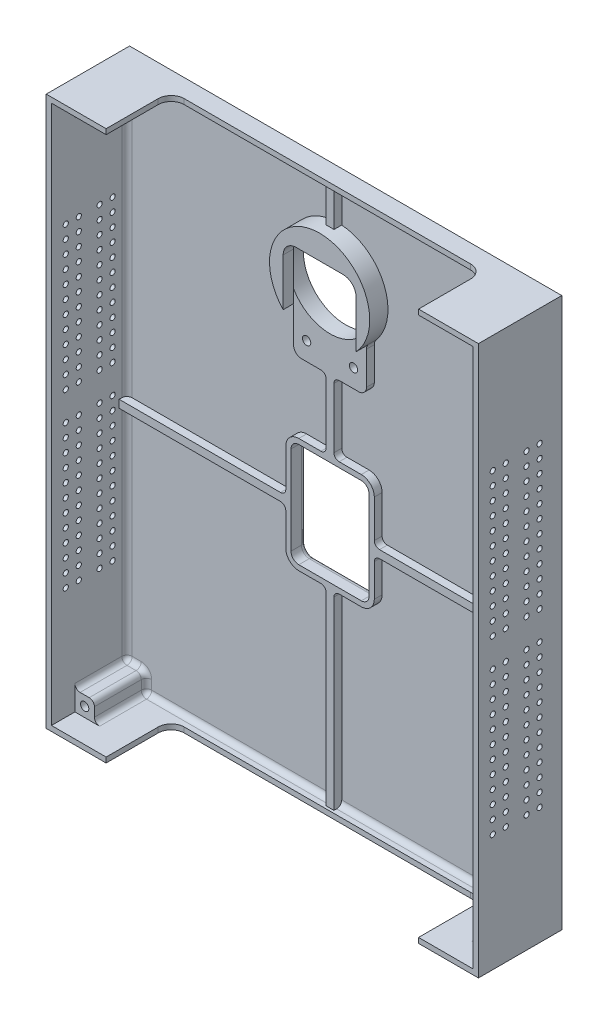
SolidWorks part; units mm, degrees
ref_plane "Front Plane" through (0, 0, 0) normal (0, 0, 1) x (1, 0, 0)
ref_plane "Top Plane" through (0, 0, 0) normal (0, 1, 0) x (1, 0, 0)
ref_plane "Right Plane" through (0, 0, 0) normal (1, 0, 0) x (0, 0, -1)
ref_plane "Plane1" through (0, 0, -1) normal (0, 0, 1) x (1, 0, 0)
sketch "Sketch5" plane through (0, 0, -1) normal (0, 0, 1) x (1, 0, 0)
  line L0 (100, 83.2573) -> (100, -169.2647) construction
  line L2 (17, 83.2573) -> (17, -127.7573)
  line L3 (17, -127.7573) -> (183, -127.7573)
  line L4 (183, 83.2573) -> (183, -127.7573)
  line L5 (17, 83.2573) -> (183, 83.2573)
  circle A0 centre (100, 48.2573) radius 16.25
  point P17 (45, 83.2573)
  dimension "D1" = 166
  dimension "D2" = 83
extrude "Boss-Extrude5" add sketch "Sketch5" along normal blind 3
sketch "Sketch6" plane through (0, 0, 2) normal (0, 0, 1) x (1, 0, 0)
  line L0 (116.25, 48.2573) -> (83.75, 48.2573) construction
  line L2 (86, 35.0451) -> (86, 18.2573)
  line L3 (86, 18.2573) -> (114, 18.2573)
  line L4 (114, 35.0451) -> (114, 18.2573)
  line L5 (100, 48.2573) -> (100, 52.872) construction
  circle A1 centre (100, 48.2573) radius 16.25
  arc A2 (114, 35.0451) -> (86, 35.0451) centre (100, 48.2573) ccw
  circle A6 centre (100, 48.2573) radius 16.25 construction
extrude "Boss-Extrude6" add sketch "Sketch6" along normal blind 3
sketch "Sketch7" plane through (0, 0, 5) normal (0, 0, 1) x (1, 0, 0)
  line L0 (114, 35.0451) -> (114, 53.2573)
  line L1 (109, 58.2573) -> (91, 58.2573)
  line L2 (86, 53.2573) -> (86, 35.0451)
  line L3 (100, 64.5073) -> (100, 48.2573) construction
  line L4 (100, 48.2573) -> (116.25, 48.2573) construction
  arc A4 (91, 58.2573) -> (86, 53.2573) centre (91, 53.2573) ccw
  arc A5 (114, 53.2573) -> (109, 58.2573) centre (109, 53.2573) ccw
  arc A8 (114, 35.0451) -> (86, 35.0451) centre (100, 48.2573) ccw
  circle A9 centre (100, 48.2573) radius 19.25 construction
  circle A10 centre (100, 48.2573) radius 16.25 construction
extrude "Boss-Extrude7" add sketch "Sketch7" along normal blind 4
sketch "Sketch8" plane through (0, 0, 2) normal (0, 0, 1) x (1, 0, 0)
  line L4 (17, -127.7573) -> (183, -127.7573)
  line L5 (183, -127.7573) -> (183, 83.2573)
  line L6 (183, 83.2573) -> (17, 83.2573)
  line L7 (17, 83.2573) -> (17, -127.7573)
  line L8 (17, -127.7573) -> (183, -127.7573)
  line L9 (183, -127.7573) -> (183, 83.2573)
  line L10 (183, 83.2573) -> (17, 83.2573)
  line L11 (17, 83.2573) -> (17, -127.7573)
  line L12 (19, -125.7573) -> (181, -125.7573)
  line L13 (181, -125.7573) -> (181, 81.2573)
  line L14 (181, 81.2573) -> (19, 81.2573)
  line L15 (19, 81.2573) -> (19, -125.7573)
  dimension "D1" = 0
  dimension "D2" = 2
extrude "Boss-Extrude8" add sketch "Sketch8" along normal blind 29
fillet "Fillet2" radius 3 4 edges at (114, 18.2573, 3.5) (114, 35.0451, 3.5) (86, 18.2573, 3.5) (86, 35.0451, 3.5)
sketch "Sketch9" plane through (0, 0, 5) normal (0, 0, 1) x (1, 0, 0)
  line L0 (100, 48.2573) -> (100, 25.2573) construction
  line L1 (91, 25.2573) -> (109, 25.2573) construction
  line L2 (100, 25.2573) -> (100, 23.2329) construction
  circle A0 centre (91, 25.2573) radius 1.6
  circle A1 centre (109, 25.2573) radius 1.6
extrude "Cut-Extrude1" cut sketch "Sketch9" against normal up to surface (6 mm away) up to face at (100, -22.25, -1)
sketch "Sketch12" plane through (183, 0, 0) normal (1, 0, 0) x (0, 0, -1)
  circle A0 centre (-12.5, -16.7427) radius 1
  circle A1 centre (-7.5, -16.7427) radius 1
  circle A2 centre (-7.5, -11.7427) radius 1
  circle A3 centre (-7.5, -6.7427) radius 1
  circle A4 centre (-7.5, -1.7427) radius 1
  circle A5 centre (-7.5, 3.2573) radius 1
  circle A6 centre (-7.5, 8.2573) radius 1
  circle A7 centre (-7.5, 13.2573) radius 1
  circle A8 centre (-7.5, 18.2573) radius 1
  circle A9 centre (-7.5, 23.2573) radius 1
  circle A10 centre (-7.5, 28.2573) radius 1
  circle A11 centre (-7.5, 33.2573) radius 1
  circle A12 centre (-7.5, 38.2573) radius 1
  circle A13 centre (-12.5, -11.7427) radius 1
  circle A14 centre (-12.5, -6.7427) radius 1
  circle A15 centre (-12.5, -1.7427) radius 1
  circle A16 centre (-12.5, 3.2573) radius 1
  circle A17 centre (-12.5, 8.2573) radius 1
  circle A18 centre (-12.5, 13.2573) radius 1
  circle A19 centre (-12.5, 18.2573) radius 1
  circle A20 centre (-12.5, 23.2573) radius 1
  circle A21 centre (-12.5, 28.2573) radius 1
  circle A22 centre (-12.5, 33.2573) radius 1
  circle A23 centre (-12.5, 38.2573) radius 1
  circle A24 centre (-12.5, -82.7573) radius 1
  circle A25 centre (-12.5, -77.7573) radius 1
  circle A26 centre (-12.5, -72.7573) radius 1
  circle A27 centre (-12.5, -67.7573) radius 1
  circle A28 centre (-12.5, -62.7573) radius 1
  circle A29 centre (-12.5, -57.7573) radius 1
  circle A30 centre (-12.5, -52.7573) radius 1
  circle A31 centre (-12.5, -47.7573) radius 1
  circle A32 centre (-12.5, -42.7573) radius 1
  circle A33 centre (-12.5, -37.7573) radius 1
  circle A34 centre (-12.5, -32.7573) radius 1
  circle A35 centre (-7.5, -82.7573) radius 1
  circle A36 centre (-7.5, -77.7573) radius 1
  circle A37 centre (-7.5, -72.7573) radius 1
  circle A38 centre (-7.5, -67.7573) radius 1
  circle A39 centre (-7.5, -62.7573) radius 1
  circle A40 centre (-7.5, -57.7573) radius 1
  circle A41 centre (-7.5, -52.7573) radius 1
  circle A42 centre (-7.5, -47.7573) radius 1
  circle A43 centre (-7.5, -42.7573) radius 1
  circle A44 centre (-7.5, -37.7573) radius 1
  circle A45 centre (-7.5, -32.7573) radius 1
  circle A46 centre (-7.5, -27.7573) radius 1
  circle A47 centre (-12.5, -27.7573) radius 1
  circle A48 centre (-20.5, -27.7573) radius 1
  circle A49 centre (-25.5, -27.7573) radius 1
  circle A50 centre (-25.5, -32.7573) radius 1
  circle A51 centre (-25.5, -37.7573) radius 1
  circle A52 centre (-25.5, -42.7573) radius 1
  circle A53 centre (-25.5, -47.7573) radius 1
  circle A54 centre (-25.5, -52.7573) radius 1
  circle A55 centre (-25.5, -57.7573) radius 1
  circle A56 centre (-25.5, -62.7573) radius 1
  circle A57 centre (-25.5, -67.7573) radius 1
  circle A58 centre (-25.5, -72.7573) radius 1
  circle A59 centre (-25.5, -77.7573) radius 1
  circle A60 centre (-25.5, -82.7573) radius 1
  circle A61 centre (-20.5, -32.7573) radius 1
  circle A62 centre (-20.5, -37.7573) radius 1
  circle A63 centre (-20.5, -42.7573) radius 1
  circle A64 centre (-20.5, -47.7573) radius 1
  circle A65 centre (-20.5, -52.7573) radius 1
  circle A66 centre (-20.5, -57.7573) radius 1
  circle A67 centre (-20.5, -62.7573) radius 1
  circle A68 centre (-20.5, -67.7573) radius 1
  circle A69 centre (-20.5, -72.7573) radius 1
  circle A70 centre (-20.5, -77.7573) radius 1
  circle A71 centre (-20.5, -82.7573) radius 1
  circle A72 centre (-20.5, 38.2573) radius 1
  circle A73 centre (-20.5, 33.2573) radius 1
  circle A74 centre (-20.5, 28.2573) radius 1
  circle A75 centre (-20.5, 23.2573) radius 1
  circle A76 centre (-20.5, 18.2573) radius 1
  circle A77 centre (-20.5, 13.2573) radius 1
  circle A78 centre (-20.5, 8.2573) radius 1
  circle A79 centre (-20.5, 3.2573) radius 1
  circle A80 centre (-20.5, -1.7427) radius 1
  circle A81 centre (-20.5, -6.7427) radius 1
  circle A82 centre (-20.5, -11.7427) radius 1
  circle A83 centre (-25.5, 38.2573) radius 1
  circle A84 centre (-25.5, 33.2573) radius 1
  circle A85 centre (-25.5, 28.2573) radius 1
  circle A86 centre (-25.5, 23.2573) radius 1
  circle A87 centre (-25.5, 18.2573) radius 1
  circle A88 centre (-25.5, 13.2573) radius 1
  circle A89 centre (-25.5, 8.2573) radius 1
  circle A90 centre (-25.5, 3.2573) radius 1
  circle A91 centre (-25.5, -1.7427) radius 1
  circle A92 centre (-25.5, -6.7427) radius 1
  circle A93 centre (-25.5, -11.7427) radius 1
  circle A94 centre (-25.5, -16.7427) radius 1
  circle A95 centre (-20.5, -16.7427) radius 1
  dimension "D1" = 2
  dimension "D2" = 12
extrude "Cut-Extrude4" cut sketch "Sketch12" against normal up to surface (2 mm away) up to face at (181, -22.25, 16.5)
sketch "Sketch13" plane through (0, 0, -1) normal (0, 0, -1) x (-1, 0, 0)
  line L0 (-183, -30.7808) -> (-100, -30.7808) construction
  line L1 (-183, -127.7573) -> (-183, 83.2573) construction
  line L6 (-100, 83.2573) -> (-100, -30.7808) construction
  line L7 (-183, 83.2573) -> (-17, 83.2573) construction
  line L14 (-85, -47.7808) -> (-85, -13.7808)
  line L15 (-88, -10.7808) -> (-112, -10.7808)
  line L16 (-115, -13.7808) -> (-115, -47.7808)
  line L17 (-112, -50.7808) -> (-88, -50.7808)
  circle A1 centre (-100, -30.7808) radius 9 construction
  arc A15 (-88, -50.7808) -> (-85, -47.7808) centre (-88, -47.7808) ccw
  arc A16 (-85, -13.7808) -> (-88, -10.7808) centre (-88, -13.7808) ccw
  arc A17 (-112, -10.7808) -> (-115, -13.7808) centre (-112, -13.7808) ccw
  arc A18 (-115, -47.7808) -> (-112, -50.7808) centre (-112, -47.7808) ccw
extrude "Cut-Extrude5" cut sketch "Sketch13" against normal blind 3
sketch "Sketch14" plane through (17, 0, 0) normal (-1, 0, 0) x (0, 0, 1)
  circle A1 centre (12.5, -82.7573) radius 1
  circle A2 centre (12.5, -82.7573) radius 1
  circle A3 centre (12.5, -16.7427) radius 1
  circle A4 centre (12.5, -16.7427) radius 1
  circle A5 centre (7.5, 18.2573) radius 1
  circle A6 centre (7.5, 18.2573) radius 1
  circle A7 centre (7.5, 13.2573) radius 1
  circle A8 centre (7.5, 13.2573) radius 1
  circle A9 centre (7.5, 8.2573) radius 1
  circle A10 centre (7.5, 8.2573) radius 1
  circle A11 centre (7.5, 3.2573) radius 1
  circle A12 centre (7.5, 3.2573) radius 1
  circle A13 centre (7.5, -1.7427) radius 1
  circle A14 centre (7.5, -1.7427) radius 1
  circle A15 centre (7.5, -6.7427) radius 1
  circle A16 centre (7.5, -6.7427) radius 1
  circle A17 centre (7.5, -11.7427) radius 1
  circle A18 centre (7.5, -11.7427) radius 1
  circle A19 centre (7.5, -16.7427) radius 1
  circle A20 centre (7.5, -16.7427) radius 1
  circle A21 centre (12.5, 3.2573) radius 1
  circle A22 centre (12.5, 3.2573) radius 1
  circle A23 centre (12.5, -1.7427) radius 1
  circle A24 centre (12.5, -1.7427) radius 1
  circle A25 centre (12.5, -6.7427) radius 1
  circle A26 centre (12.5, -6.7427) radius 1
  circle A27 centre (12.5, -11.7427) radius 1
  circle A28 centre (12.5, -11.7427) radius 1
  circle A29 centre (7.5, 38.2573) radius 1
  circle A30 centre (7.5, 38.2573) radius 1
  circle A31 centre (7.5, 33.2573) radius 1
  circle A32 centre (7.5, 33.2573) radius 1
  circle A33 centre (7.5, 28.2573) radius 1
  circle A34 centre (7.5, 28.2573) radius 1
  circle A35 centre (7.5, 23.2573) radius 1
  circle A36 centre (7.5, 23.2573) radius 1
  circle A37 centre (12.5, -77.7573) radius 1
  circle A38 centre (12.5, -77.7573) radius 1
  circle A39 centre (12.5, 38.2573) radius 1
  circle A40 centre (12.5, 38.2573) radius 1
  circle A41 centre (12.5, 33.2573) radius 1
  circle A42 centre (12.5, 33.2573) radius 1
  circle A43 centre (12.5, 28.2573) radius 1
  circle A44 centre (12.5, 28.2573) radius 1
  circle A45 centre (12.5, 23.2573) radius 1
  circle A46 centre (12.5, 23.2573) radius 1
  circle A47 centre (12.5, 18.2573) radius 1
  circle A48 centre (12.5, 18.2573) radius 1
  circle A49 centre (12.5, 13.2573) radius 1
  circle A50 centre (12.5, 13.2573) radius 1
  circle A51 centre (12.5, 8.2573) radius 1
  circle A52 centre (12.5, 8.2573) radius 1
  circle A53 centre (12.5, -37.7573) radius 1
  circle A54 centre (12.5, -37.7573) radius 1
  circle A55 centre (12.5, -42.7573) radius 1
  circle A56 centre (12.5, -42.7573) radius 1
  circle A57 centre (12.5, -47.7573) radius 1
  circle A58 centre (12.5, -47.7573) radius 1
  circle A59 centre (12.5, -52.7573) radius 1
  circle A60 centre (12.5, -52.7573) radius 1
  circle A61 centre (12.5, -57.7573) radius 1
  circle A62 centre (12.5, -57.7573) radius 1
  circle A63 centre (12.5, -62.7573) radius 1
  circle A64 centre (12.5, -62.7573) radius 1
  circle A65 centre (12.5, -67.7573) radius 1
  circle A66 centre (12.5, -67.7573) radius 1
  circle A67 centre (12.5, -72.7573) radius 1
  circle A68 centre (12.5, -72.7573) radius 1
  circle A69 centre (7.5, -52.7573) radius 1
  circle A70 centre (7.5, -52.7573) radius 1
  circle A71 centre (7.5, -57.7573) radius 1
  circle A72 centre (7.5, -57.7573) radius 1
  circle A73 centre (7.5, -62.7573) radius 1
  circle A74 centre (7.5, -62.7573) radius 1
  circle A75 centre (7.5, -67.7573) radius 1
  circle A76 centre (7.5, -67.7573) radius 1
  circle A77 centre (7.5, -72.7573) radius 1
  circle A78 centre (7.5, -72.7573) radius 1
  circle A79 centre (7.5, -77.7573) radius 1
  circle A80 centre (7.5, -77.7573) radius 1
  circle A81 centre (7.5, -82.7573) radius 1
  circle A82 centre (7.5, -82.7573) radius 1
  circle A83 centre (12.5, -32.7573) radius 1
  circle A84 centre (12.5, -32.7573) radius 1
  circle A85 centre (25.5, -27.7573) radius 1
  circle A86 centre (25.5, -27.7573) radius 1
  circle A87 centre (20.5, -27.7573) radius 1
  circle A88 centre (20.5, -27.7573) radius 1
  circle A89 centre (12.5, -27.7573) radius 1
  circle A90 centre (12.5, -27.7573) radius 1
  circle A91 centre (7.5, -27.7573) radius 1
  circle A92 centre (7.5, -27.7573) radius 1
  circle A93 centre (7.5, -32.7573) radius 1
  circle A94 centre (7.5, -32.7573) radius 1
  circle A95 centre (7.5, -37.7573) radius 1
  circle A96 centre (7.5, -37.7573) radius 1
  circle A97 centre (7.5, -42.7573) radius 1
  circle A98 centre (7.5, -42.7573) radius 1
  circle A99 centre (7.5, -47.7573) radius 1
  circle A100 centre (7.5, -47.7573) radius 1
  circle A101 centre (25.5, -67.7573) radius 1
  circle A102 centre (25.5, -67.7573) radius 1
  circle A103 centre (25.5, -62.7573) radius 1
  circle A104 centre (25.5, -62.7573) radius 1
  circle A105 centre (25.5, -57.7573) radius 1
  circle A106 centre (25.5, -57.7573) radius 1
  circle A107 centre (25.5, -52.7573) radius 1
  circle A108 centre (25.5, -52.7573) radius 1
  circle A109 centre (25.5, -47.7573) radius 1
  circle A110 centre (25.5, -47.7573) radius 1
  circle A111 centre (25.5, -42.7573) radius 1
  circle A112 centre (25.5, -42.7573) radius 1
  circle A113 centre (25.5, -37.7573) radius 1
  circle A114 centre (25.5, -37.7573) radius 1
  circle A115 centre (25.5, -32.7573) radius 1
  circle A116 centre (25.5, -32.7573) radius 1
  circle A117 centre (20.5, -52.7573) radius 1
  circle A118 centre (20.5, -52.7573) radius 1
  circle A119 centre (20.5, -47.7573) radius 1
  circle A120 centre (20.5, -47.7573) radius 1
  circle A121 centre (20.5, -42.7573) radius 1
  circle A122 centre (20.5, -42.7573) radius 1
  circle A123 centre (20.5, -37.7573) radius 1
  circle A124 centre (20.5, -37.7573) radius 1
  circle A125 centre (20.5, -32.7573) radius 1
  circle A126 centre (20.5, -32.7573) radius 1
  circle A127 centre (25.5, -82.7573) radius 1
  circle A128 centre (25.5, -82.7573) radius 1
  circle A129 centre (25.5, -77.7573) radius 1
  circle A130 centre (25.5, -77.7573) radius 1
  circle A131 centre (25.5, -72.7573) radius 1
  circle A132 centre (25.5, -72.7573) radius 1
  circle A133 centre (20.5, 33.2573) radius 1
  circle A134 centre (20.5, 33.2573) radius 1
  circle A135 centre (20.5, 38.2573) radius 1
  circle A136 centre (20.5, 38.2573) radius 1
  circle A137 centre (20.5, -82.7573) radius 1
  circle A138 centre (20.5, -82.7573) radius 1
  circle A139 centre (20.5, -77.7573) radius 1
  circle A140 centre (20.5, -77.7573) radius 1
  circle A141 centre (20.5, -72.7573) radius 1
  circle A142 centre (20.5, -72.7573) radius 1
  circle A143 centre (20.5, -67.7573) radius 1
  circle A144 centre (20.5, -67.7573) radius 1
  circle A145 centre (20.5, -62.7573) radius 1
  circle A146 centre (20.5, -62.7573) radius 1
  circle A147 centre (20.5, -57.7573) radius 1
  circle A148 centre (20.5, -57.7573) radius 1
  circle A149 centre (20.5, -6.7427) radius 1
  circle A150 centre (20.5, -6.7427) radius 1
  circle A151 centre (20.5, -1.7427) radius 1
  circle A152 centre (20.5, -1.7427) radius 1
  circle A153 centre (20.5, 3.2573) radius 1
  circle A154 centre (20.5, 3.2573) radius 1
  circle A155 centre (20.5, 8.2573) radius 1
  circle A156 centre (20.5, 8.2573) radius 1
  circle A157 centre (20.5, 13.2573) radius 1
  circle A158 centre (20.5, 13.2573) radius 1
  circle A159 centre (20.5, 18.2573) radius 1
  circle A160 centre (20.5, 18.2573) radius 1
  circle A161 centre (20.5, 23.2573) radius 1
  circle A162 centre (20.5, 23.2573) radius 1
  circle A163 centre (20.5, 28.2573) radius 1
  circle A164 centre (20.5, 28.2573) radius 1
  circle A165 centre (25.5, 8.2573) radius 1
  circle A166 centre (25.5, 8.2573) radius 1
  circle A167 centre (25.5, 13.2573) radius 1
  circle A168 centre (25.5, 13.2573) radius 1
  circle A169 centre (25.5, 18.2573) radius 1
  circle A170 centre (25.5, 18.2573) radius 1
  circle A171 centre (25.5, 23.2573) radius 1
  circle A172 centre (25.5, 23.2573) radius 1
  circle A173 centre (25.5, 28.2573) radius 1
  circle A174 centre (25.5, 28.2573) radius 1
  circle A175 centre (25.5, 33.2573) radius 1
  circle A176 centre (25.5, 33.2573) radius 1
  circle A177 centre (25.5, 38.2573) radius 1
  circle A178 centre (25.5, 38.2573) radius 1
  circle A179 centre (20.5, -11.7427) radius 1
  circle A180 centre (20.5, -11.7427) radius 1
  circle A181 centre (20.5, -16.7427) radius 1
  circle A182 centre (20.5, -16.7427) radius 1
  circle A183 centre (25.5, -16.7427) radius 1
  circle A184 centre (25.5, -16.7427) radius 1
  circle A185 centre (25.5, -11.7427) radius 1
  circle A186 centre (25.5, -11.7427) radius 1
  circle A187 centre (25.5, -6.7427) radius 1
  circle A188 centre (25.5, -6.7427) radius 1
  circle A189 centre (25.5, -1.7427) radius 1
  circle A190 centre (25.5, -1.7427) radius 1
  circle A191 centre (25.5, 3.2573) radius 1
  circle A192 centre (25.5, 3.2573) radius 1
  dimension "D1" = 0
  dimension "D2" = 0
  dimension "D3" = 0
  dimension "D4" = 0
  dimension "D5" = 0
  dimension "D6" = 0
  dimension "D7" = 0
  dimension "D8" = 0
  dimension "D9" = 0
  dimension "D10" = 0
  dimension "D11" = 0
  dimension "D12" = 0
  dimension "D13" = 0
  dimension "D14" = 0
  dimension "D15" = 0
  dimension "D16" = 0
  dimension "D17" = 0
  dimension "D18" = 0
  dimension "D19" = 0
  dimension "D20" = 0
  dimension "D21" = 0
  dimension "D22" = 0
  dimension "D23" = 0
  dimension "D24" = 0
  dimension "D25" = 0
  dimension "D26" = 0
  dimension "D27" = 0
  dimension "D28" = 0
  dimension "D29" = 0
  dimension "D30" = 0
  dimension "D31" = 0
  dimension "D32" = 0
  dimension "D33" = 0
  dimension "D34" = 0
  dimension "D35" = 0
  dimension "D36" = 0
  dimension "D37" = 0
  dimension "D38" = 0
  dimension "D39" = 0
  dimension "D40" = 0
  dimension "D41" = 0
  dimension "D42" = 0
  dimension "D43" = 0
  dimension "D44" = 0
  dimension "D45" = 0
  dimension "D46" = 0
  dimension "D47" = 0
  dimension "D48" = 0
  dimension "D49" = 0
  dimension "D50" = 0
  dimension "D51" = 0
  dimension "D52" = 0
  dimension "D53" = 0
  dimension "D54" = 0
  dimension "D55" = 0
  dimension "D56" = 0
  dimension "D57" = 0
  dimension "D58" = 0
  dimension "D59" = 0
  dimension "D60" = 0
  dimension "D61" = 0
  dimension "D62" = 0
  dimension "D63" = 0
  dimension "D64" = 0
  dimension "D65" = 0
  dimension "D66" = 0
  dimension "D67" = 0
  dimension "D68" = 0
  dimension "D69" = 0
  dimension "D70" = 0
  dimension "D71" = 0
  dimension "D72" = 0
  dimension "D73" = 0
  dimension "D74" = 0
  dimension "D75" = 0
  dimension "D76" = 0
  dimension "D77" = 0
  dimension "D78" = 0
  dimension "D79" = 0
  dimension "D80" = 0
  dimension "D81" = 0
  dimension "D82" = 0
  dimension "D83" = 0
  dimension "D84" = 0
  dimension "D85" = 0
  dimension "D86" = 0
  dimension "D87" = 0
  dimension "D88" = 0
  dimension "D89" = 0
  dimension "D90" = 0
  dimension "D91" = 0
  dimension "D92" = 0
  dimension "D93" = 0
  dimension "D94" = 0
  dimension "D95" = 0
  dimension "D96" = 0
extrude "Cut-Extrude6" cut sketch "Sketch14" against normal up to surface (2 mm away) up to face at (19, -22.25, 16.5)
sketch "Sketch15" plane through (0, -127.7573, 0) normal (0, -1, 0) x (1, 0, 0)
  line L5 (100, -1) -> (100, 31) construction
  line L6 (17, -1) -> (183, -1) construction
  line L7 (17, 31) -> (183, 31) construction
  line L8 (40, 31) -> (160, 31)
  line L9 (40, 31) -> (40, 11)
  line L10 (45, 6) -> (155, 6)
  line L11 (160, 31) -> (160, 11)
  arc A4 (155, 6) -> (160, 11) centre (155, 11) ccw
  arc A5 (40, 11) -> (45, 6) centre (45, 11) ccw
  point P12 (160, 6)
  point P15 (40, 6)
  dimension "D4" = 5
  dimension "D1" = 60
  dimension "D2" = 120
  dimension "D3" = 25
extrude "Cut-Extrude7" cut sketch "Sketch15" against normal up to surface (2 mm away) up to face at (100, -125.7573, 16.5)
sketch "Sketch16" plane through (0, 83.2573, 0) normal (0, 1, 0) x (1, 0, 0)
  line L4 (40, -31) -> (160, -31)
  line L5 (40, -31) -> (160, -31)
  line L6 (160, -31) -> (160, -11)
  line L7 (160, -31) -> (160, -11)
  line L12 (155, -6) -> (45, -6)
  line L13 (155, -6) -> (45, -6)
  line L14 (40, -11) -> (40, -31)
  line L15 (40, -11) -> (40, -31)
  arc A2 (160, -11) -> (155, -6) centre (155, -11) ccw
  arc A3 (160, -11) -> (155, -6) centre (155, -11) ccw
  arc A4 (45, -6) -> (40, -11) centre (45, -11) ccw
  arc A5 (45, -6) -> (40, -11) centre (45, -11) ccw
  dimension "D1" = 0
extrude "Cut-Extrude8" cut sketch "Sketch16" against normal up to surface (2 mm away) up to face at (100, 81.2573, 16.5)
sketch "Sketch18" plane through (0, 0, 2) normal (0, 0, 1) x (1, 0, 0)
  line L1 (19, -125.7573) -> (26.5, -125.7573)
  line L2 (19, -125.7573) -> (19, -118.2573)
  line L3 (19, -118.2573) -> (26.5, -118.2573)
  line L4 (26.5, -125.7573) -> (26.5, -118.2573)
  line L5 (181, -125.7573) -> (173.5, -125.7573)
  line L6 (181, -125.7573) -> (181, -118.2573)
  line L7 (181, -118.2573) -> (173.5, -118.2573)
  line L8 (173.5, -125.7573) -> (173.5, -118.2573)
  line L9 (19, 81.2573) -> (26.5, 81.2573)
  line L10 (19, 81.2573) -> (19, 73.7573)
  line L11 (19, 73.7573) -> (26.5, 73.7573)
  line L12 (26.5, 81.2573) -> (26.5, 73.7573)
  line L13 (181, 81.2573) -> (173.5, 81.2573)
  line L14 (181, 81.2573) -> (181, 73.7573)
  line L15 (181, 73.7573) -> (173.5, 73.7573)
  line L16 (173.5, 81.2573) -> (173.5, 73.7573)
extrude "Boss-Extrude10" add sketch "Sketch18" along normal blind 20
fillet "Fillet3" radius 2 12 edges at (181, 73.7573, 12) (173.5, 73.7573, 12) (173.5, 81.2573, 12) (26.5, 81.2573, 12) (26.5, 73.7573, 12) (19, 73.7573, 12) (19, -118.2573, 12) (26.5, -118.2573, 12) (26.5, -125.7573, 12) (181, -118.2573, 12) (173.5, -118.2573, 12) (173.5, -125.7573, 12)
sketch "Sketch19" plane through (0, 0, 22) normal (0, 0, 1) x (1, 0, 0)
  line L4 (100, -127.7573) -> (100, 83.2573) construction
  line L5 (45, -127.7573) -> (155, -127.7573) construction
  line L6 (155, 83.2573) -> (45, 83.2573) construction
  line L7 (100, -22.25) -> (17, -22.25) construction
  line L8 (17, 83.2573) -> (17, -127.7573) construction
  circle A0 centre (22.75, -122.0073) radius 1.6
  circle A1 centre (177.25, -122.0073) radius 1.6
  circle A2 centre (177.25, 77.5073) radius 1.6
  circle A3 centre (22.75, 77.5073) radius 1.6
extrude "Cut-Extrude9" cut sketch "Sketch19" against normal up to surface (23 mm away) up to face at (100, -30.7808, -1)
fillet "Fillet4" radius 2 24 edges at (180.4142, -117.6715, 2) (177.25, -118.2573, 2) (174.0858, -118.8431, 2) (173.5, -122.0073, 2) (172.9142, -125.1715, 2) (100, -125.7573, 2) (27.0858, -125.1715, 2) (26.5, -122.0073, 2) (25.9142, -118.8431, 2) (22.75, -118.2573, 2) (19.5858, -117.6715, 2) (19, -22.25, 2) (19.5858, 73.1715, 2) (22.75, 73.7573, 2) (25.9142, 74.3431, 2) (26.5, 77.5073, 2) (27.0858, 80.6715, 2) (100, 81.2573, 2) (172.9142, 80.6715, 2) (173.5, 77.5073, 2) (174.0858, 74.3431, 2) (177.25, 73.7573, 2) (180.4142, 73.1715, 2) (181, -22.25, 2)
sketch "Sketch20" plane through (0, 0, 2) normal (0, 0, 1) x (1, 0, 0)
  line L0 (83, -30.2573) -> (83, -13.7808)
  line L1 (155, 83.2573) -> (45, 83.2573) construction
  line L2 (45, -127.7573) -> (155, -127.7573) construction
  line L3 (88, -10.7808) -> (112, -10.7808) construction
  line L4 (101.5, -127.7573) -> (98.5, -127.7573)
  line L5 (101.5, -127.7573) -> (101.5, -52.7808)
  line L6 (101.5, 83.2573) -> (98.5, 83.2573)
  line L7 (98.5, -127.7573) -> (98.5, -52.7808)
  line L8 (115, -13.7808) -> (115, -47.7808) construction
  line L9 (112, -50.7808) -> (88, -50.7808) construction
  line L10 (85, -47.7808) -> (85, -13.7808) construction
  line L11 (88, -10.7808) -> (112, -10.7808)
  line L12 (115, -13.7808) -> (115, -47.7808)
  line L13 (112, -50.7808) -> (88, -50.7808)
  line L14 (85, -47.7808) -> (85, -13.7808)
  line L15 (88, -8.7808) -> (98.5, -8.7808)
  line L16 (117, -13.7808) -> (117, -30.2573)
  line L17 (112, -52.7808) -> (101.5, -52.7808)
  line L18 (83, -47.7808) -> (83, -33.2573)
  line L19 (101.5, -8.7808) -> (112, -8.7808)
  line L20 (183, -127.7573) -> (183, 83.2573) construction
  line L21 (183, -33.2573) -> (117, -33.2573)
  line L22 (183, -33.2573) -> (183, -30.2573)
  line L23 (183, -30.2573) -> (117, -30.2573)
  line L24 (17, -33.2573) -> (17, -30.2573)
  line L25 (17, 83.2573) -> (17, -127.7573) construction
  line L26 (83, -33.2573) -> (17, -33.2573)
  line L28 (98.5, -52.7808) -> (88, -52.7808)
  line L31 (83, -30.2573) -> (17, -30.2573)
  line L32 (98.5, -8.7808) -> (98.5, 18.2573)
  line L33 (112, -52.7808) -> (88, -52.7808) construction
  line L35 (117, -33.2573) -> (117, -47.7808)
  line L37 (101.5, -8.7808) -> (101.5, 18.2573)
  line L38 (117, -13.7808) -> (117, -47.7808) construction
  line L39 (88, -8.7808) -> (112, -8.7808) construction
  line L40 (83, -47.7808) -> (83, -13.7808) construction
  line L42 (89, 18.2573) -> (111, 18.2573) construction
  line L43 (98.5, 18.2573) -> (101.5, 18.2573)
  line L44 (98.5, 64.4379) -> (98.5, 83.2573)
  line L45 (101.5, 64.4379) -> (101.5, 83.2573)
  line L49 (114, 53.2573) -> (114, 40.0073)
  line L50 (91, 58.2573) -> (109, 58.2573)
  line L51 (86, 40.0073) -> (86, 53.2573)
  arc A0 (88, -10.7808) -> (85, -13.7808) centre (88, -13.7808) ccw construction
  arc A1 (115, -13.7808) -> (112, -10.7808) centre (112, -13.7808) ccw construction
  arc A2 (112, -50.7808) -> (115, -47.7808) centre (112, -47.7808) ccw construction
  arc A3 (85, -47.7808) -> (88, -50.7808) centre (88, -47.7808) ccw construction
  arc A4 (88, -10.7808) -> (85, -13.7808) centre (88, -13.7808) ccw
  arc A5 (115, -13.7808) -> (112, -10.7808) centre (112, -13.7808) ccw
  arc A6 (112, -50.7808) -> (115, -47.7808) centre (112, -47.7808) ccw
  arc A7 (85, -47.7808) -> (88, -50.7808) centre (88, -47.7808) ccw
  arc A8 (117, -13.7808) -> (112, -8.7808) centre (112, -13.7808) ccw
  arc A9 (112, -52.7808) -> (117, -47.7808) centre (112, -47.7808) ccw
  arc A10 (83, -47.7808) -> (88, -52.7808) centre (88, -47.7808) ccw
  arc A11 (88, -8.7808) -> (83, -13.7808) centre (88, -13.7808) ccw
  arc A15 (114, 40.0073) -> (86, 40.0073) centre (100, 48.2573) ccw
  arc A16 (114, 53.2573) -> (109, 58.2573) centre (109, 53.2573) ccw
  arc A17 (91, 58.2573) -> (86, 53.2573) centre (91, 53.2573) ccw
  arc A18 (101.5, 64.4379) -> (98.5, 64.4379) centre (100, 48.2573) ccw
  dimension "D1" = 0
  dimension "D3" = 2
extrude "Boss-Extrude11" add sketch "Sketch20" along normal blind 3
fillet "Fillet5" radius 2 10 edges at (98.5, -52.7808, 3.5) (101.5, -52.7808, 3.5) (117, -33.2573, 3.5) (117, -30.2573, 3.5) (83, -33.2573, 3.5) (83, -30.2573, 3.5) (98.5, -8.7808, 3.5) (101.5, -8.7808, 3.5) (98.5, 18.2573, 3.5) (101.5, 18.2573, 3.5)
sketch "Sketch21" plane through (0, 0, -1) normal (0, 0, -1) x (-1, 0, 0)
  circle A0 centre (-109, 25.2573) radius 2.25
  circle A1 centre (-91, 25.2573) radius 2.25
extrude "Cut-Extrude10" cut sketch "Sketch21" against normal blind 3
fillet "Fillet6" radius 2 8 edges at (85.8787, -49.9021, -1) (100, -50.7808, -1) (114.1213, -49.9021, -1) (115, -30.7808, -1) (114.1213, -11.6594, -1) (100, -10.7808, -1) (85.8787, -11.6594, -1) (85, -30.7808, -1)
